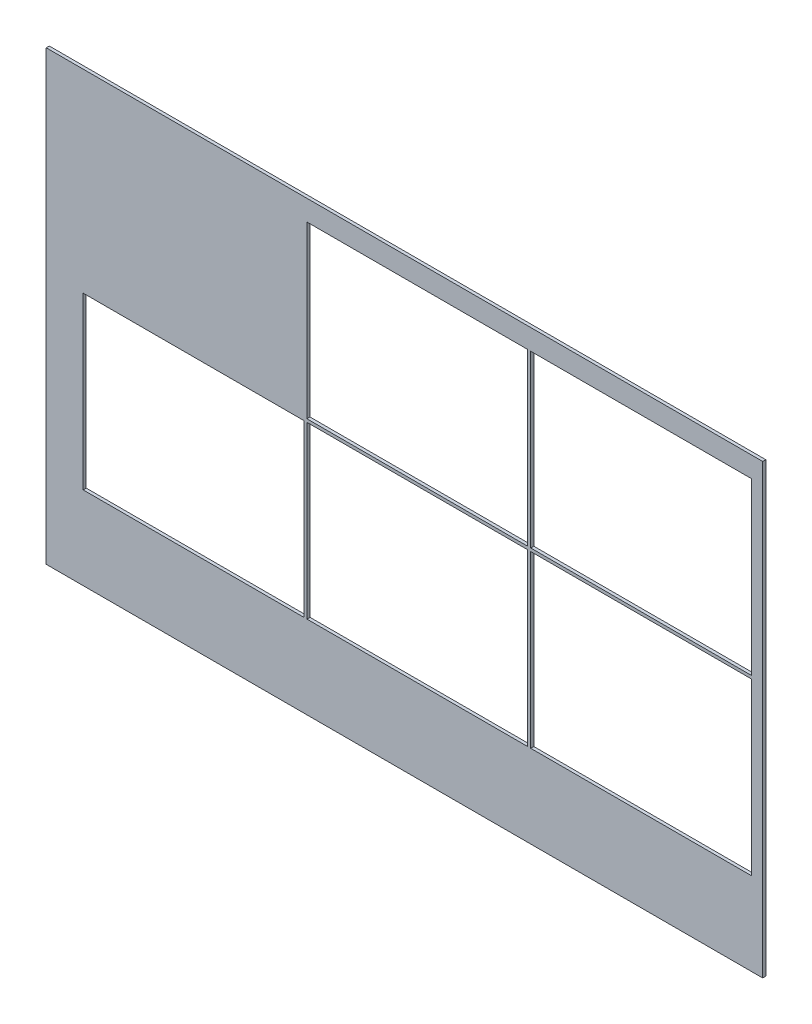
SolidWorks part; units mm, degrees
ref_plane "Спереди" through (0, 0, 0) normal (0, 0, 1) x (1, 0, 0)
ref_plane "Сверху" through (0, 0, 0) normal (0, 1, 0) x (1, 0, 0)
ref_plane "Справа" through (0, 0, 0) normal (1, 0, 0) x (0, 0, -1)
sketch "Эскиз1" plane through (0, 0, 0) normal (0, 0, 1) x (1, 0, 0)
  line L1 (447, 435.8) -> (447, -435.8) construction
  line L2 (447, -435.8) -> (-949, -435.8)
  line L3 (447, -435.8) -> (447, 435.8)
  line L4 (447, 435.8) -> (-949, 435.8)
  line L5 (-949, -435.8) -> (-949, 435.8)
  line L6 (441, -435.8) -> (447, -435.8) construction
extrude "Бобышка-Вытянуть1" add sketch "Эскиз1" against normal blind 6
sketch "Эскиз2" plane through (0, 0, 0) normal (0, 0, 1) x (1, 0, 0)
  line L1 (-441, 395.8) -> (-11, 395.8)
  line L2 (-441, 395.8) -> (-441, 63.8)
  line L3 (-441, 63.8) -> (-11, 63.8)
  line L4 (-11, 395.8) -> (-11, 63.8)
  dimension "D1" = 430
  dimension "D2" = 332
extrude "Вырез-Вытянуть1" cut sketch "Эскиз2" against normal through all
pattern_linear "Линейный массив1" count 2 spacing 436 along (1, 0, 0) count 2 spacing 338 along (0, -1, 0) of "Вырез-Вытянуть1"
sketch "Эскиз3" plane through (0, 0, 0) normal (0, 0, 1) x (1, 0, 0)
  line L1 (-447, -274.2) -> (-877, -274.2)
  line L2 (-447, -274.2) -> (-447, 57.8)
  line L3 (-447, 57.8) -> (-877, 57.8)
  line L4 (-877, -274.2) -> (-877, 57.8)
  line L5 (-441, 57.8) -> (-441, -274.2) construction
  line L6 (-11, 57.8) -> (-441, 57.8) construction
  dimension "D1" = 430
  dimension "D2" = 332
  dimension "D3" = 6
extrude "Вырез-Вытянуть2" cut sketch "Эскиз3" against normal through all
equation "\"Ширина груза\"= 420"
equation "\"Глубина груза\"= 490"
equation "\"Высота груза\"= 297"
equation "\"Ширина ячейки\"= \"Ширина груза\" + 10"
equation "\"Глубина ячейки\"= \"Глубина груза\" + 10"
equation "\"Высота ячейки\"= \"Высота груза\" + 10 + 13"
equation "\"Колво ячеек ширина\"= 2"
equation "\"Колво ячеек высота\"= 2"
equation "\"Толщина стенки\" = 6"
equation "\"Крепление дверцы\"= 5 "
equation "\"Ширина рейки\"= \"Толщина шестерни\""
equation "\"Высота рейки\"= 20"
equation "\"Высота пола\"= \"Толщина стенки\" * 2"
equation "\"Колво полозьев\"= 5"
equation "\"Отступ рейки\"= 20"
equation "\"Глубина каретки\"= \"Глубина ячейки\" + 30 + \"Мотор Y высота корпуса\" + 20"
equation "\"Длинна рейки\"= ( \"Ширина ячейки\" + \"Толщина стенки\" + \"Крепление дверцы\" ) * \"Колво ячеек ширина\" + \"Ширина ячейки выгрузки\" * \"Колво выгрузки\" + \"Толщина стенки\""
equation "\"Отступ шпильки\"= 26"
equation "\"Диаметр шпильки\"= 5"
equation "\"Длинна шпильки\"= ( \"Высота ячейки\" + \"Толщина стенки\" + \"Высота пола\" ) * \"Колво ячеек высота\" + ( \"Толщина стенки\" + \"Отступ рейки\" ) * 2 "
equation "\"Ширина пластины\"= 50  "
equation "\"Высота зона выгрузки\"= \"Высота ячейки\" * 2 + \"Толщина стенки\" * 2"
equation "\"Колво выгрузки\"= 1"
equation "\"Ширина ячейки выгрузки\"= \"Ширина ячейки\" + \"Толщина стенки\" + \"Отступ крепления мотора фиксации\"*2"
equation "\"Отступ крепления мотора фиксации\" = 30"
equation "\"Мотор X ширина корпуса\"= 42.3"
equation "\"Мотор X высота корпуса\"= 42.3"
equation "\"Мотор X длина корпуса\"= 40"
equation "\"Мотор X вылет вала\"= 19.8"
equation "\"Мотор Y ширина корпуса\"= 42.3"
equation "\"Мотор Y высота корпуса\"= 42.3"
equation "\"Мотор Y длина корпуса\"= 48"
equation "\"Мотор Y вылет вала\"= 30"
equation "\"Мотор Z ширина корпуса\"= 42"
equation "\"Мотор Z высота корпуса\"= 42"
equation "\"Мотор Z длина корпуса\"= 40"
equation "\"Мотор Z вылет вала\"= 23"
equation "\"Мотор диаметр вала ПРЕДВ\"= 5"
equation "\"Мотор шаг крепления ПРЕДВ\"= 31"
equation "\"Мотор диаметр отверстий ПРЕДВ\"= 3"
equation "\"Мотор глубина отверстий ПРЕДВ\"= 4.5"
equation "\"Мотор диаметр буртика ПРЕДВ\"= 22"
equation "\"Мотор высота буртика ПРЕДВ\"= 2"
equation "\"Мотор диаметр шкива ПРЕДВ\"= 16"
equation "\"Мотор длина шкива ПРЕДВ\"= 12"
equation "\"Мотор отступ шкива ПРЕДВ\"= 5"
equation "\"Мотор X шаг градусов\"= 1.8"
equation "\"Мотор Y шаг градусов\"= 1.8"
equation "\"Мотор Z шаг градусов\"= 1.8"
equation "\"Мотор Y диаметр ротора\"= 25.78"
equation "\"Толщина шестерни\"= 10"
equation "\"D1@Бобышка-Вытянуть1\"=\"Толщина стенки\""
equation "\"D1@Эскиз2\"=\"Ширина ячейки\""
equation "\"D2@Эскиз2\"=\"Высота ячейки\" + \"Высота пола\""
equation "\"D3@Линейный массив1\"=\"Ширина ячейки\" + \"Толщина стенки\""
equation "\"D4@Линейный массив1\"=\"Высота ячейки\" + \"Высота пола\" + \"Толщина стенки\""
equation "\"D1@Эскиз3\"=\"Ширина ячейки\""
equation "\"D2@Эскиз3\"=\"Высота ячейки\" + \"Высота пола\""
equation "\"D3@Эскиз3\"=\"Толщина стенки\""
